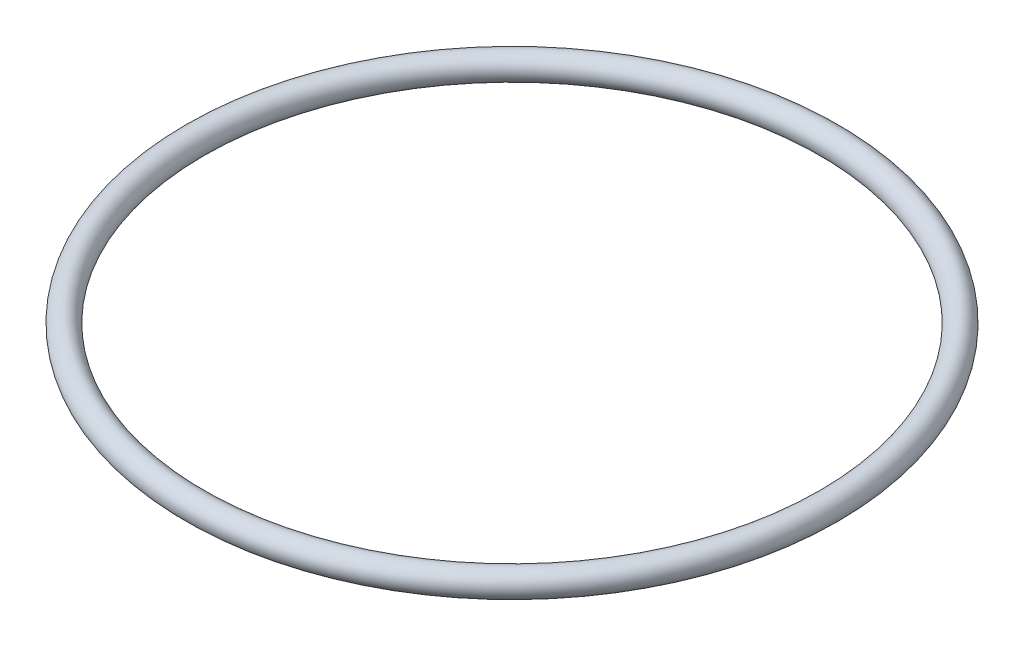
SolidWorks part; units mm, degrees
ref_plane "Front Plane" through (0, 0, 0) normal (0, 0, 1) x (1, 0, 0)
ref_plane "Top Plane" through (0, 0, 0) normal (0, 1, 0) x (1, 0, 0)
ref_plane "Right Plane" through (0, 0, 0) normal (1, 0, 0) x (0, 0, -1)
sketch "Sketch1" plane through (0, 0, 0) normal (0, 0, 1) x (1, 0, 0)
  line L0 (0, 46.363) -> (0, -45.3801)
  circle A0 centre (12.5, 0) radius 0.5
revolve "Revolve1" add sketch "Sketch1" angle 360 about L0
sketch "Sketch2" plane through (0, 0, 0) normal (0, 1, 0) x (1, 0, 0)
  circle A0 centre (0, 0) radius 7.75
sketch "Sketch3" plane through (0, 0, 0) normal (1, 0, 0) x (0, 0, -1)
  line L0 (0, 2.704) -> (0, -2.6818) construction
ref_axis "Axis1" through (0, 2.704, 0) along (0, -1, 0)
sketch "Sketch4" plane through (0, 0, 0) normal (1, 0, 0) x (0, 0, -1)
  point P4 (-8.2489, 0)
  point P5 (8.25, 0)
ref_point "Point2"
